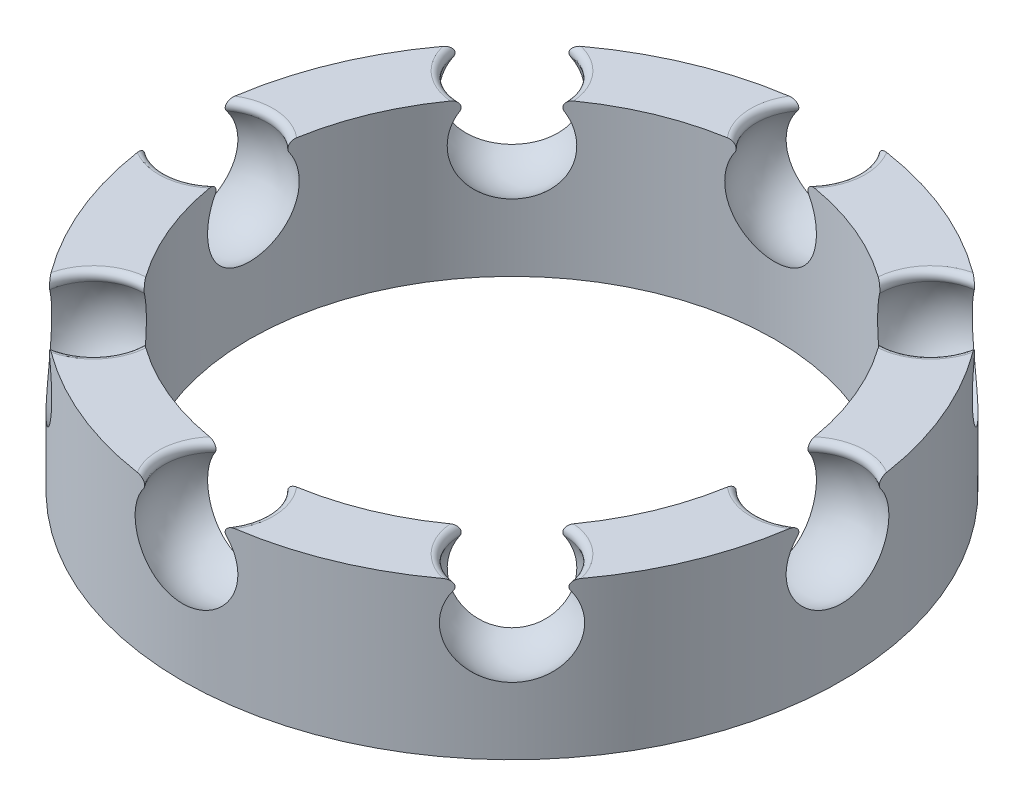
SolidWorks part; units mm, degrees
ref_plane "Спереди" through (0, 0, 0) normal (0, 0, 1) x (1, 0, 0)
ref_plane "Сверху" through (0, 0, 0) normal (0, 1, 0) x (1, 0, 0)
ref_plane "Справа" through (0, 0, 0) normal (1, 0, 0) x (0, 0, -1)
sketch "Эскиз1" plane through (0, 0, 0) normal (0, 0, 1) x (1, 0, 0)
  line L0 (0, 13.8117) -> (0, -21.5589) construction
  line L1 (12.8, 0) -> (10.2, 0)
  line L2 (12.8, 0) -> (12.8, 6)
  line L3 (12.8, 6) -> (10.2, 6)
  line L4 (10.2, 0) -> (10.2, 6)
  line L5 (11.5, 6.8) -> (11.5, 2.2)
  circle A0 centre (11.5, 4.5) radius 2.3
  point P4 (11.5, 0)
  point P9 (11.5, 6)
  dimension "D4" = 4.6
  dimension "D1" = 10.2
  dimension "D2" = 2.6
  dimension "D3" = 6
  dimension "D5" = 4.5
revolve "Повернуть1" add sketch "Эскиз1" angle 360 about L0 region at (11.5, 1.1676, 0) region at (12.1384, 4.1627, 0) region at (10.8616, 4.1627, 0)
revolve "Вырез-Повернуть2" cut sketch "Эскиз1<5>" angle 360 about L5 region at (12.1384, 4.1627, 0) region at (12.9319, 4.9551, 0)
sketch "Эскиз1<5>" plane through (0, 0, 0) normal (0, 0, 1) x (1, 0, 0) same geometry as "Эскиз1"
fillet "Скругление1" radius 0.25 2 edges at (11.4118, 6, 1.7413) (11.4118, 6, -1.7413)
pattern_circular "Круговой массив2" count 8 over 360 about axis through (0, 6, 0) along (0, 1, 0) of "Скругление1", "Вырез-Повернуть2"
